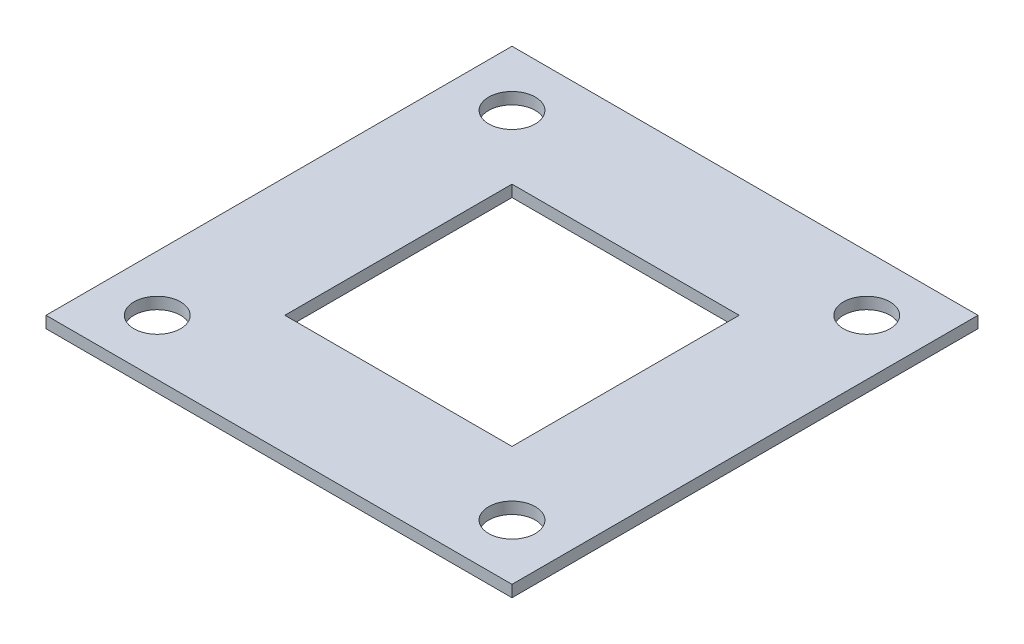
SolidWorks part; units mm, degrees
ref_plane "前视基准面" through (0, 0, 0) normal (0, 0, 1) x (1, 0, 0)
ref_plane "上视基准面" through (0, 0, 0) normal (0, 1, 0) x (1, 0, 0)
ref_plane "右视基准面" through (0, 0, 0) normal (1, 0, 0) x (0, 0, -1)
sketch "草图2" plane through (0, 0, 0) normal (0, 1, 0) x (1, 0, 0)
  line L0 (0, 0) -> (31.047, 0) construction
  line L1 (-9.75, -9.75) -> (9.75, -9.75)
  line L2 (-9.75, -9.75) -> (-9.75, 9.75)
  line L3 (-9.75, 9.75) -> (9.75, 9.75)
  line L4 (9.75, -9.75) -> (9.75, 9.75)
  line L5 (-9.75, -9.75) -> (9.75, 9.75) construction
  line L6 (-9.75, 9.75) -> (9.75, -9.75) construction
  line L7 (-20, -20) -> (20, -20)
  line L8 (-20, -20) -> (-20, 20)
  line L9 (-20, 20) -> (20, 20)
  line L10 (20, -20) -> (20, 20)
  line L11 (-20, -20) -> (20, 20) construction
  line L12 (-20, 20) -> (20, -20) construction
  line L13 (0, 0) -> (0, 17.7315) construction
  circle A0 centre (15.2248, 15.2248) radius 2
  circle A1 centre (-15.2248, -15.2248) radius 2
  circle A2 centre (15.2248, -15.2248) radius 2
  circle A3 centre (-15.2248, 15.2248) radius 2
  point P0 (0, 0)
  point P6 (0, 0)
  dimension "D5" = 4
  dimension "D1" = 19.5
  dimension "D2" = 19.5
  dimension "D3" = 40
  dimension "D4" = 40
  dimension "D6" = 21.5311
extrude "凸台-拉伸2" add sketch "草图2" along normal blind 1 contours L8 L9 L10 L7
sketch "草图3" plane through (0, 0, 0) normal (0, 1, 0) x (1, 0, 0)
  line L7 (8, 6.0116) -> (11, 6.0116)
  line L8 (8, 6.0116) -> (8, -5.9884)
  line L9 (8, -5.9884) -> (11, -5.9884)
  line L10 (11, 6.0116) -> (11, -5.9884)
  circle A0 centre (-15.2248, -15.2248) radius 2 construction
  circle A1 centre (15.2248, -15.2248) radius 2 construction
  circle A2 centre (15.2248, 15.2248) radius 2 construction
  circle A3 centre (-15.2248, 15.2248) radius 2 construction
  circle A4 centre (-15.2248, -15.2248) radius 2
  circle A5 centre (15.2248, -15.2248) radius 2
  circle A6 centre (15.2248, 15.2248) radius 2
  circle A7 centre (-15.2248, 15.2248) radius 2
  circle A8 centre (-7, 0) radius 5.125
  point P15 (0, 0)
  point P27 (8, 0.0116)
  dimension "D1" = 10.25
  dimension "D2" = 8
  dimension "D5" = 12
  dimension "D6" = 3
sketch "草图4" plane through (0, 0, 0) normal (0, 1, 0) x (1, 0, 0)
  line L0 (0, 0) -> (31.047, 0) construction
  circle A0 centre (3, 0) radius 2
  dimension "D1" = 4
  dimension "D2" = 3
sketch "草图9" plane through (0, 1, 0) normal (0, 1, 0) x (1, 0, 0)
  line L1 (20, -20) -> (-20, -20)
  line L2 (20, -20) -> (20, 20)
  line L3 (20, 20) -> (-20, 20)
  line L4 (-20, -20) -> (-20, 20)
extrude "切除-拉伸2" cut sketch "草图3" along normal blind 10 contours A5 | A6 | A7 | A4
extrude "切除-拉伸3" cut sketch "草图2<10>" along normal blind 10 contours L1 L4 L3 L2
sketch "草图2<10>" plane through (0, 0, 0) normal (0, 1, 0) x (1, 0, 0) same geometry as "草图2"
